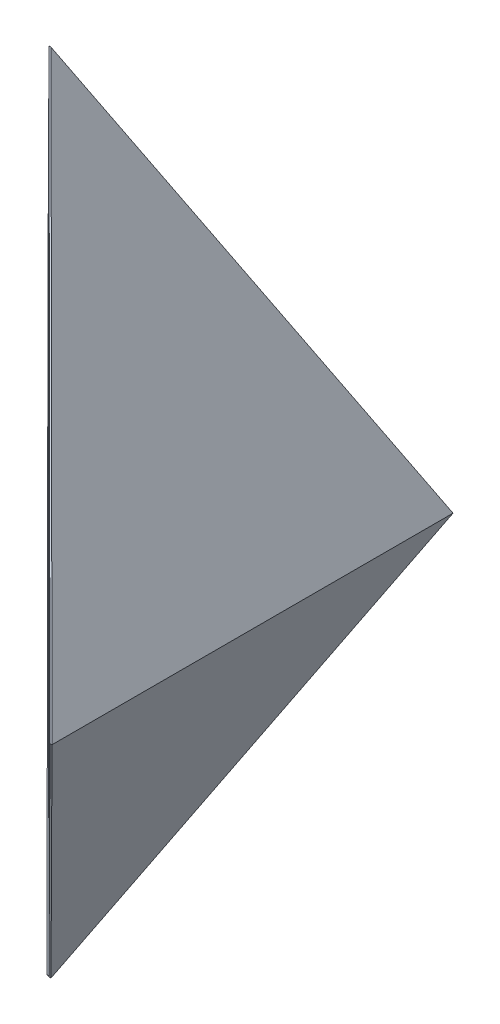
SolidWorks part; units mm, degrees
ref_plane "Płaszczyzna przednia" through (0, 0, 0) normal (0, 0, 1) x (1, 0, 0)
ref_plane "Płaszczyzna górna" through (0, 0, 0) normal (0, 1, 0) x (1, 0, 0)
ref_plane "Płaszczyzna prawa" through (0, 0, 0) normal (1, 0, 0) x (0, 0, -1)
sketch "Szkic2" plane through (0, 0, 0) normal (0, 0, 1) x (1, 0, 0)
  line L0 (0, 0) -> (0, 20) construction
  line L1 (0, 0) -> (0, -20) construction
  line L2 (0, 0) -> (10, 0) construction
  line L3 (0, 0) -> (-10, 0) construction
  line L4 (0, 20) -> (-10, 0)
  line L5 (-10, 0) -> (-9.2466, -0.6605)
  line L6 (-10, 0) -> (0, -20)
  line L7 (0, -20) -> (10, 0)
  line L8 (10, 0) -> (0, 20)
  dimension "D1" = 20
  dimension "D2" = 20
  dimension "D3" = 10
  dimension "D4" = 10
extrude "Dodanie-wyciągnięcie1" add sketch "Szkic2" along normal blind 20 contours L7 L8 L4 L6 region at (0, 0, 0)
sketch "Szkic6" plane through (0, 0, 0) normal (1, 0, 0) x (0, 0, -1)
  line L0 (0, 0) -> (-0.1, 0) construction
  line L1 (-20, 0) -> (0, 0) construction
  line L2 (-0.1, 0) -> (-10, 0) construction
  line L3 (-10, 0) -> (-19.9, 0) construction
  line L4 (-10, 0) -> (-10, 19.9) construction
  line L5 (-10, 0) -> (-10, -19.9) construction
  line L6 (-10, 19.9) -> (-19.9, 0)
  line L7 (-19.9, 0) -> (-10, -19.9)
  line L8 (-10, -19.9) -> (-0.1, 0)
  line L9 (-0.1, 0) -> (-10, 19.9)
  line L10 (-20, 0) -> (-20, 20)
  line L11 (-20, 20) -> (0, 20)
  line L12 (0, 20) -> (0, -20)
  line L13 (0, -20) -> (-20, -20)
  line L14 (-20, -20) -> (-20, 0)
  dimension "D1" = 0.1
  dimension "D2" = 9.9
  dimension "D3" = 19.9
  dimension "D4" = 19.9
extrude "Wytnij-wyciągnięcie2" cut sketch "Szkic6" against normal blind 10 and the other way blind 10
ref_plane "Płaszczyzna1" through (-5.0248, 0, 5.0502) normal (0.7053, 0, -0.7089) x (-0.7089, 0, -0.7053)
sketch "Szkic7" plane through (-5.0248, 0, 5.0502) normal (0.7053, 0, -0.7089) x (-0.7089, 0, -0.7053)
  line L0 (7.0183, 0) -> (-7.0178, 19.9)
  line L1 (-7.0178, 19.9) -> (-21.1248, 0)
  line L2 (-21.1248, 0) -> (-7.0887, -19.9)
  line L3 (-7.0887, -19.9) -> (7.0183, 0)
extrude "Wytnij-wyciągnięcie3" cut sketch "Szkic7" against normal blind 40
sketch "Szkic8" plane through (-5.0248, 0, 5.0502) normal (-0.7053, 0, 0.7089) x (0.7089, 0, 0.7053)
  line L0 (-7.0183, 0) -> (21.0539, 0)
  line L1 (7.0178, 19.9) -> (7.0178, -19.9)
  line L2 (-7.0183, 0) -> (7.0178, -19.9) construction
  point P9 (7.0178, 0)
